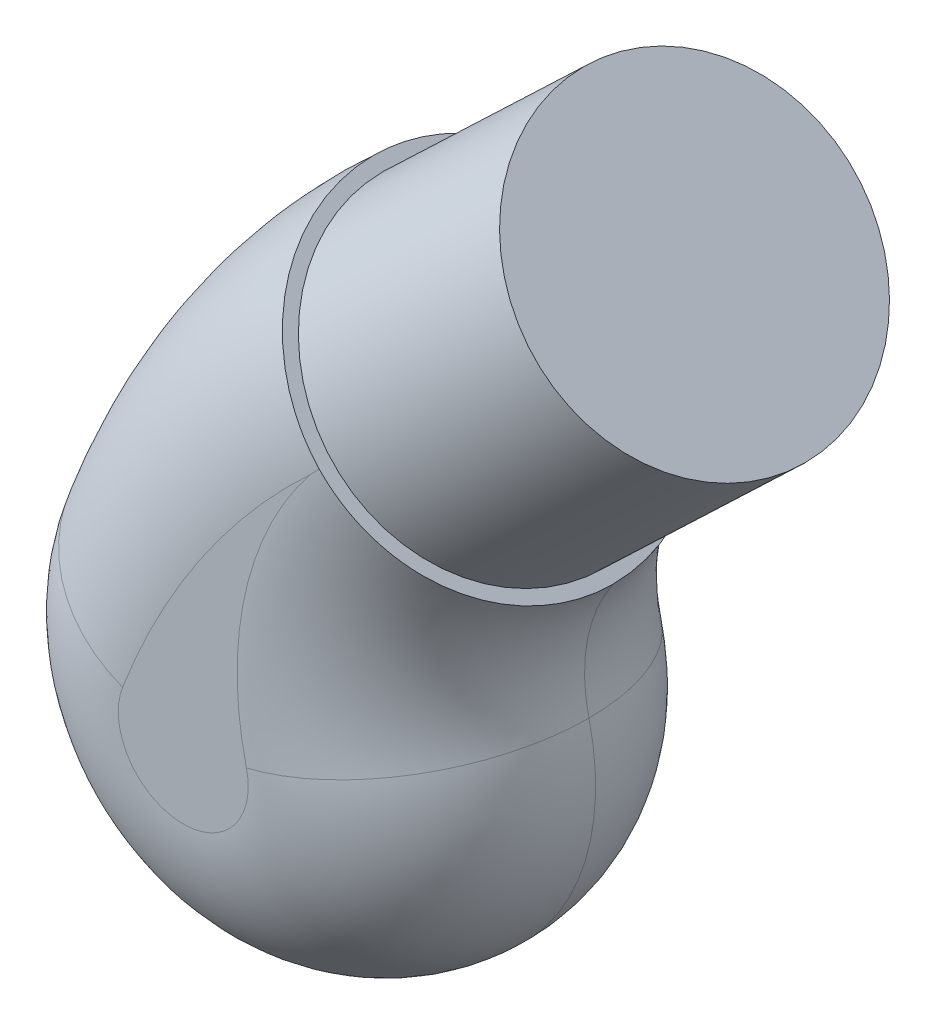
SolidWorks part; units mm, degrees
material "POLYURETHANE (11671)"
ref_plane "Front" through (0, 0, 0) normal (0, 0, 1) x (1, 0, 0)
ref_plane "Top" through (0, 0, 0) normal (0, 1, 0) x (1, 0, 0)
ref_plane "Right" through (0, 0, 0) normal (1, 0, 0) x (0, 0, -1)
sketch "Sketch2" plane through (0, 0, 0) normal (0, 0, 1) x (1, 0, 0)
  line L0 (18.4393, 13.2537) -> (1.1916, 31.351)
  circle A0 centre (0, 0) radius 17.175
  circle A1 centre (27.7919, 6.7088) radius 11.4151
  circle A2 centre (45.2723, -17.2723) radius 65.6303
  dimension "D1" = 25
extrude "Boss-Extrude1" add sketch "Sketch2" along normal blind 25 contours L0 A2 A0 A1 | A0 region at (3.1098, 19.6572, 0)
fillet "Fillet1" radius 12.5 6 edges at (16.5755, 8.8295, 25) (-1.0951, -17.1401, 25) (16.5755, 8.8295, 0) (-1.0951, -17.1401, 0) (-8.9163, 19.7538, 25) (-8.9163, 19.7538, 0)
sketch "Sketch3" plane through (16.2818, 15.5174, 0) normal (0.7239, 0.6899, 0) x (0, 0, -1)
  spline S8 degree 3 poles (470.8704, -1918.3455) (142.1469, -292.1278) (35.387, 30.5768) (-15.0987, 20.5814) (-15.4617, 20.4911) (-16.1814, 20.2739) (-16.5392, 20.1464) (-17.5803, 19.7167) (-18.2388, 19.3661) (-19.1738, 18.7449) (-19.4775, 18.5212) (-20.0627, 18.0435) (-20.3413, 17.7922) (-21.1363, 17.0019) (-21.6123, 16.4269) (-22.2436, 15.4909) (-22.44, 15.1661) (-22.7964, 14.5061) (-23.1187, 13.8321) (-23.3742, 13.1306) (-23.5957, 12.4151) (-23.6899, 12.0489) (-37.1651, -53.6949) (522.8982, -184.618) (1929.1159, -412.26) knots -8.433814 -8.433814 -8.433814 -8.433814 0.125 0.125 0.1875 0.1875 0.25 0.25 0.375 0.375 0.4375 0.4375 0.5 0.5 0.625 0.625 0.6875 0.6875 0.75 0.8125 0.8125 0.875 0.875 11.920575 11.920575 11.920575 11.920575 only from (-12.5, 20.8728) to (-23.9999, 9.4343)
  spline S9 degree 3 poles (1913.0358, 501.5415) (278.4061, 163.0534) (-33.7831, 56.828) (-23.6961, 6.824) (-23.6042, 6.4596) (-23.384, 5.7373) (-23.2551, 5.378) (-22.8213, 4.3321) (-22.4684, 3.6705) (-21.6369, 2.4179) (-21.1532, 1.8234) (-20.0964, 0.7554) (-19.5203, 0.2754) (-18.583, -0.3614) (-18.2572, -0.5603) (-17.5946, -0.921) (-17.2563, -1.0839) (-16.221, -1.5218) (-15.5022, -1.7464) (48.7247, -14.8753) (170.1136, 523.3398) (385.4703, 1955.9993) knots -8.316475 -8.316475 -8.316475 -8.316475 0.125 0.125 0.1875 0.1875 0.25 0.25 0.375 0.375 0.5 0.5 0.625 0.625 0.6875 0.6875 0.75 0.75 0.875 0.875 11.53272 11.53272 11.53272 11.53272 only from (-23.9999, 9.4343) to (-12.5, -2.1272)
  spline S10 degree 3 poles (-493.6047, 1937.6832) (-161.8856, 296.3176) (-58.812, -11.7529) (-9.8912, -1.8274) (-9.5271, -1.7346) (-8.8053, -1.5116) (-8.447, -1.381) (-7.4054, -0.9416) (-6.7469, -0.5838) (-5.8121, 0.0487) (-5.508, 0.2767) (-4.9252, 0.7603) (-4.6477, 1.0146) (-3.8554, 1.8136) (-3.3806, 2.3943) (-2.7505, 3.3393) (-2.5554, 3.6655) (-2.2006, 4.3289) (-1.8795, 5.0065) (-1.6246, 5.7119) (-1.4034, 6.4315) (-1.3094, 6.8) (11.3709, 69.0824) (-483.6251, 191.0102) (-1954.729, 428.349) knots -8.138111 -8.138111 -8.138111 -8.138111 0.125 0.125 0.1875 0.1875 0.25 0.25 0.375 0.375 0.4375 0.4375 0.5 0.5 0.625 0.625 0.6875 0.6875 0.75 0.8125 0.8125 0.875 0.875 11.29869 11.29869 11.29869 11.29869 only from (-12.5, -2.1272) to (-1.0001, 9.4245)
  spline S11 degree 3 poles (-1937.7719, -483.578) (-312.6718, -146.6641) (8.9295, -38.4052) (-1.3042, 12.0232) (-1.3962, 12.3859) (-1.6168, 13.1049) (-1.7462, 13.4623) (-2.1811, 14.502) (-2.535, 15.1593) (-3.1608, 16.0919) (-3.3859, 16.3946) (-3.8667, 16.9781) (-4.1196, 17.2555) (-4.9141, 18.0472) (-5.4916, 18.5207) (-6.4312, 19.1477) (-6.757, 19.3428) (-7.4192, 19.6961) (-7.7573, 19.8555) (-8.4468, 20.1411) (-8.7984, 20.2671) (-9.5153, 20.485) (-9.8821, 20.5771) (-75.4679, 33.6503) (-202.3342, -523.6627) (-421.511, -1934.9096) knots -8.427828 -8.427828 -8.427828 -8.427828 0.125 0.125 0.1875 0.1875 0.25 0.25 0.375 0.375 0.4375 0.4375 0.5 0.5 0.625 0.625 0.6875 0.6875 0.75 0.75 0.8125 0.8125 0.875 0.875 11.874084 11.874084 11.874084 11.874084 only from (-1.0001, 9.4245) to (-12.5, 20.8728)
  spline S12 degree 3 poles (-12.5, 20.8728) (-13.2567, 20.8728) (-14.0007, 20.7988) (-15.0987, 20.5814) (-15.4617, 20.4911) (-16.1814, 20.2739) (-16.5392, 20.1464) (-17.5803, 19.7167) (-18.2388, 19.3661) (-19.1738, 18.7449) (-19.4775, 18.5212) (-20.0627, 18.0435) (-20.3413, 17.7922) (-21.1363, 17.0019) (-21.6123, 16.4269) (-22.2436, 15.4909) (-22.44, 15.1661) (-22.7964, 14.5061) (-23.1187, 13.8321) (-23.3742, 13.1306) (-23.5957, 12.4151) (-23.6899, 12.0489) (-23.9173, 10.9392) (-23.9955, 10.191) (-23.9999, 9.4343) knots 0 0 0 0 0.125 0.125 0.1875 0.1875 0.25 0.25 0.375 0.375 0.4375 0.4375 0.5 0.5 0.625 0.625 0.6875 0.6875 0.75 0.8125 0.8125 0.875 0.875 1 1 1 1
  spline S13 degree 3 poles (-23.9999, 9.4343) (-23.9961, 8.6739) (-23.9185, 7.9265) (-23.6961, 6.824) (-23.6042, 6.4596) (-23.384, 5.7373) (-23.2551, 5.378) (-22.8213, 4.3321) (-22.4684, 3.6705) (-21.6369, 2.4179) (-21.1532, 1.8234) (-20.0964, 0.7554) (-19.5203, 0.2754) (-18.583, -0.3614) (-18.2572, -0.5603) (-17.5946, -0.921) (-17.2563, -1.0839) (-16.221, -1.5218) (-15.5022, -1.7464) (-14.0131, -2.0508) (-13.2605, -2.1272) (-12.5, -2.1272) knots 0 0 0 0 0.125 0.125 0.1875 0.1875 0.25 0.25 0.375 0.375 0.5 0.5 0.625 0.625 0.6875 0.6875 0.75 0.75 0.875 0.875 1 1 1 1
  spline S14 degree 3 poles (-12.5, -2.1272) (-11.74, -2.1272) (-10.993, -2.051) (-9.8912, -1.8274) (-9.5271, -1.7346) (-8.8053, -1.5116) (-8.447, -1.381) (-7.4054, -0.9416) (-6.7469, -0.5838) (-5.8121, 0.0487) (-5.508, 0.2767) (-4.9252, 0.7603) (-4.6477, 1.0146) (-3.8554, 1.8136) (-3.3806, 2.3943) (-2.7505, 3.3393) (-2.5554, 3.6655) (-2.2006, 4.3289) (-1.8795, 5.0065) (-1.6246, 5.7119) (-1.4034, 6.4315) (-1.3094, 6.8) (-1.0827, 7.9137) (-1.0045, 8.6647) (-1.0001, 9.4245) knots 0 0 0 0 0.125 0.125 0.1875 0.1875 0.25 0.25 0.375 0.375 0.4375 0.4375 0.5 0.5 0.625 0.625 0.6875 0.6875 0.75 0.8125 0.8125 0.875 0.875 1 1 1 1
  spline S15 degree 3 poles (-1.0001, 9.4245) (-1.0039, 10.1816) (-1.1203, 11.2977) (-1.3962, 12.3859) (-1.6168, 13.1049) (-1.7462, 13.4623) (-2.1811, 14.502) (-2.535, 15.1593) (-3.1608, 16.0919) (-3.3859, 16.3946) (-3.8667, 16.9781) (-4.1196, 17.2555) (-4.9141, 18.0472) (-5.4916, 18.5207) (-6.4312, 19.1477) (-6.757, 19.3428) (-7.4192, 19.6961) (-7.7573, 19.8555) (-8.4468, 20.1411) (-8.7984, 20.2671) (-9.5153, 20.485) (-9.8821, 20.5771) (-10.9938, 20.7987) (-11.7429, 20.8728) (-12.5, 20.8728) knots 0 0 0 0 0.125 0.1875 0.1875 0.25 0.25 0.375 0.375 0.4375 0.4375 0.5 0.5 0.625 0.625 0.6875 0.6875 0.75 0.75 0.8125 0.8125 0.875 0.875 1 1 1 1
  dimension "D1" = 1
extrude "Boss-Extrude2" add sketch "Sketch3" along normal blind 20
sketch "Sketch4" plane through (30.7597, 29.3157, 0) normal (0.7239, 0.6899, 0) x (0, 0, -1)
  circle A0 centre (-12.5068, 9.3648) radius 11.55
  dimension "D1" = 23.1
extrude "Boss-Extrude3" add sketch "Sketch4" against normal blind 20
